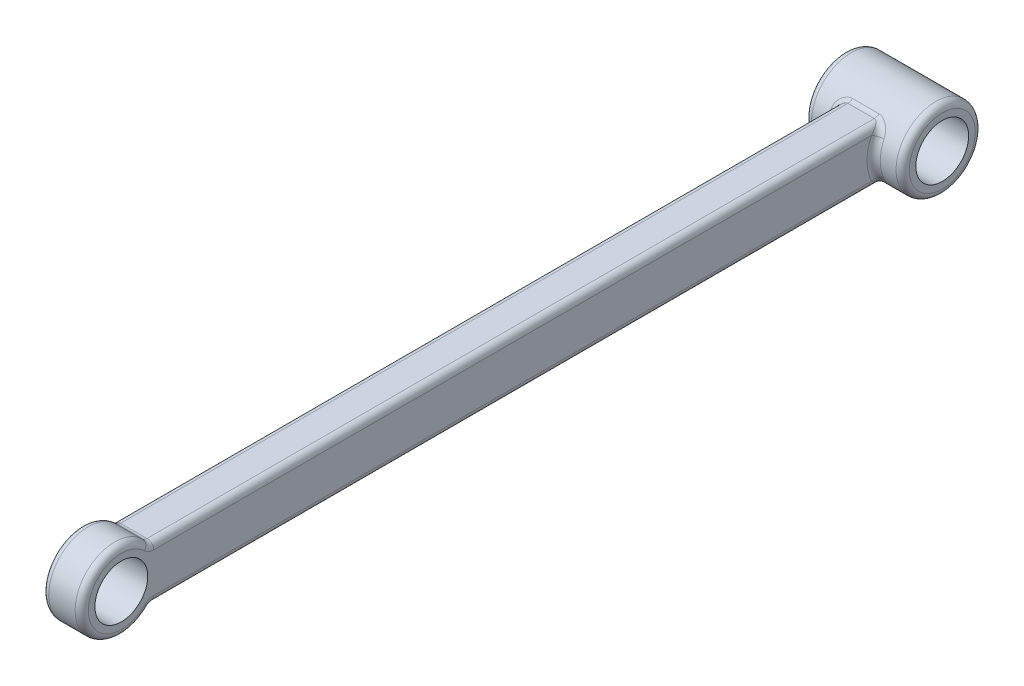
SolidWorks part; units mm, degrees
ref_plane "Front Plane" through (0, 0, 0) normal (0, 0, 1) x (1, 0, 0)
ref_plane "Top Plane" through (0, 0, 0) normal (0, 1, 0) x (1, 0, 0)
ref_plane "Right Plane" through (0, 0, 0) normal (1, 0, 0) x (0, 0, -1)
sketch "Sketch1" plane through (0, 0, 0) normal (1, 0, 0) x (0, 0, -1)
  line L0 (0, 0) -> (-60, 0) construction
  line L1 (-60, 0) -> (0, 0) construction
  line L2 (-57.7639, 2) -> (-2.2361, 2)
  line L3 (-57.7639, -2) -> (-2.2361, -2)
  arc A6 (-57.7639, 2) -> (-57.7639, -2) centre (-60, 0) ccw
  arc A7 (-2.2361, -2) -> (-2.2361, 2) centre (0, 0) ccw
  point P3 (-32, 0)
  dimension "D1" = 60
  dimension "D4" = 6
  dimension "D3" = 6
  dimension "D6" = 2
extrude "Boss-Extrude2" add sketch "Sketch1" along normal blind 3 contours L3 A7 L2 A6
sketch "Sketch2" plane through (0, 0, 0) normal (1, 0, 0) x (0, 0, -1)
  circle A0 centre (-60, 0) radius 2
  circle A1 centre (0, 0) radius 2
  dimension "D1" = 4
  dimension "D2" = 4
extrude "Cut-Extrude1" cut sketch "Sketch2" along normal blind 3 contours A1 | A0
sketch "Sketch3" plane through (0, 0, 0) normal (1, 0, 0) x (0, 0, -1)
  circle A0 centre (0, 0) radius 3
  circle A1 centre (0, 0) radius 2
extrude "Boss-Extrude3" add sketch "Sketch3" along normal blind 5.2 and the other way blind 2.2
fillet "Fillet1" radius 0.5 14 edges at (3, 0, 63) (0, 0, 63) (5.2, 0, -3) (-2.2, 0, -3) (3, 0, 3) (0, 0, 3) (1.5, 2, 2.2361) (3, 2, 30) (1.5, 2, 57.7639) (0, 2, 30) (1.5, -2, 57.7639) (3, -2, 30) (1.5, -2, 2.2361) (0, -2, 30)
scale "Scale1" scale about origin uniform scaling yes scale factor 1.5
